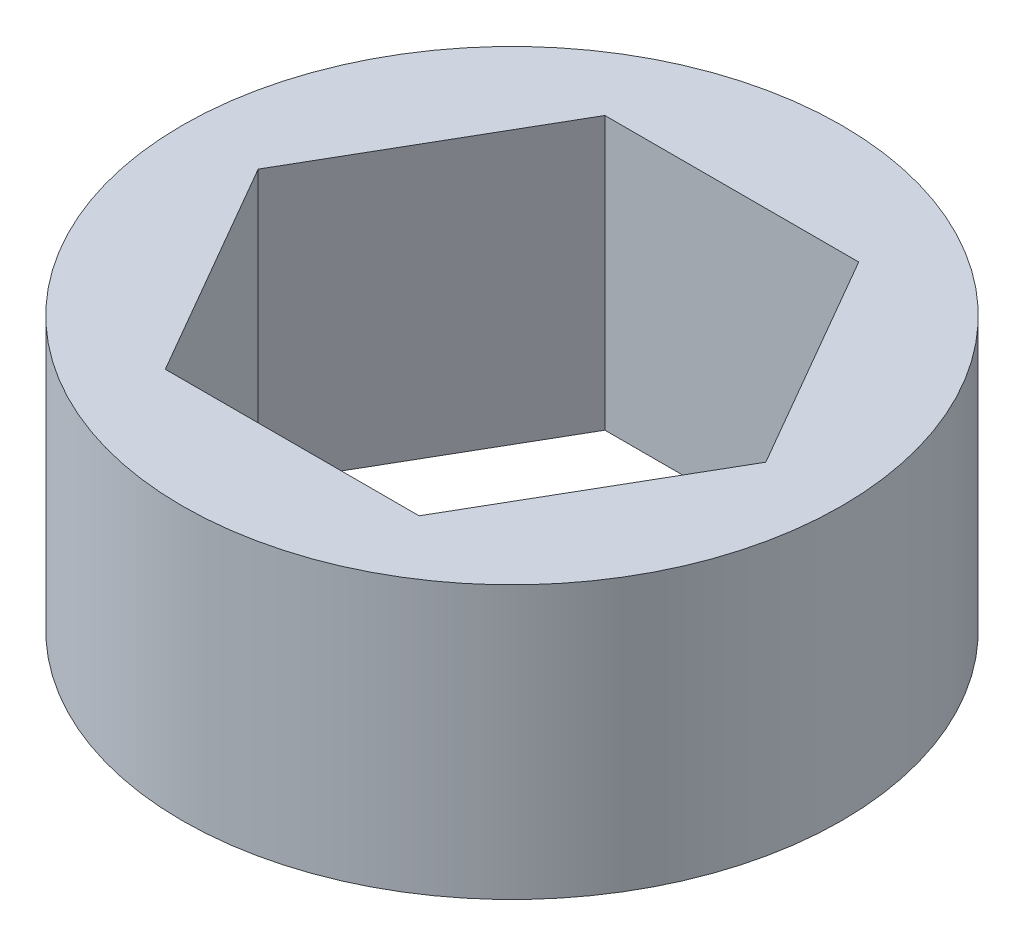
SolidWorks part; units mm, degrees
material "PET"
ref_plane "Front" through (0, 0, 0) normal (0, 0, 1) x (1, 0, 0)
ref_plane "Top" through (0, 0, 0) normal (0, 1, 0) x (1, 0, 0)
ref_plane "Right" through (0, 0, 0) normal (1, 0, 0) x (0, 0, -1)
sketch "Sketch1" plane through (0, 0, 0) normal (0, 1, 0) x (1, 0, 0)
  line L1 (3.6662, 6.35) -> (-3.6662, 6.35)
  line L2 (-3.6662, 6.35) -> (-7.3323, 0)
  line L3 (-7.3323, 0) -> (-3.6662, -6.35)
  line L4 (-3.6662, -6.35) -> (3.6662, -6.35)
  line L5 (3.6662, -6.35) -> (7.3323, 0)
  line L6 (7.3323, 0) -> (3.6662, 6.35)
  circle A0 centre (0, 0) radius 6.35 construction
  circle A2 centre (0, 0) radius 9.525
  point P1 (0, 6.35)
  dimension "D2" = 3.175
  dimension "D1" = 12.7
extrude "Boss-Extrude1" add sketch "Sketch1" along normal blind 7.874
